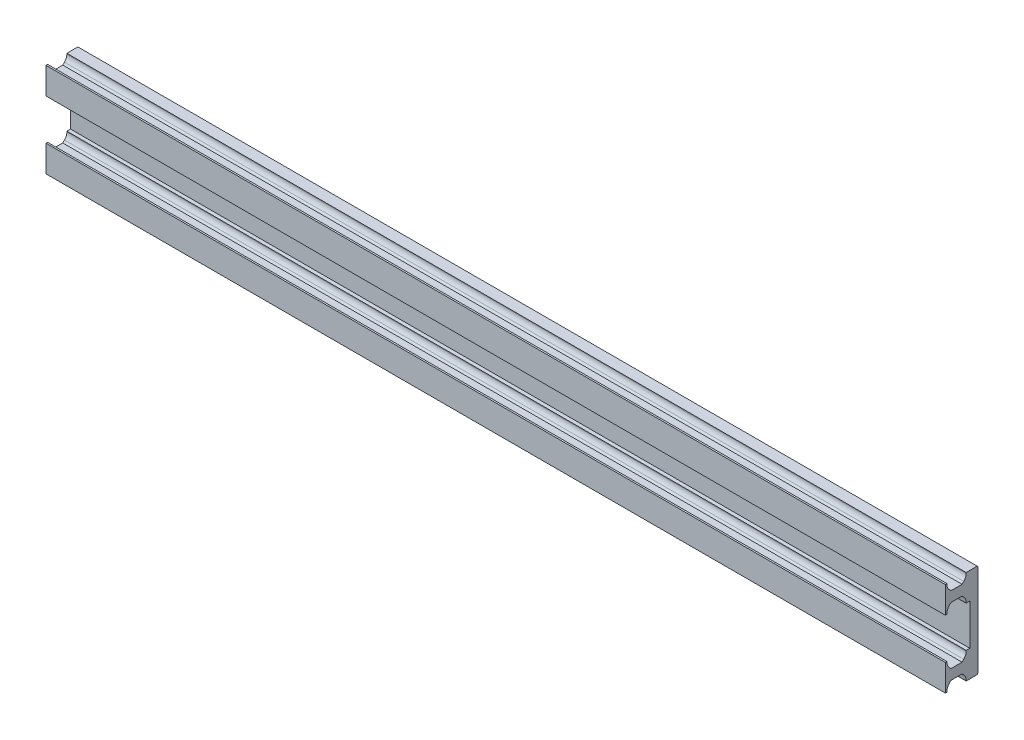
SolidWorks part; units mm, degrees
ref_plane "Front" through (0, 0, 0) normal (0, 0, 1) x (1, 0, 0)
ref_plane "Top" through (0, 0, 0) normal (0, 1, 0) x (1, 0, 0)
ref_plane "Right" through (0, 0, 0) normal (1, 0, 0) x (0, 0, -1)
sketch "Sketch1" plane through (0, 0, 0) normal (0, 0, 1) x (1, 0, 0)
  line L0 (-110, -4.5) -> (-110, 4.5) construction
  line L1 (110, 11.5) -> (-110, 11.5)
  line L2 (110, 11.5) -> (110, -11.5)
  line L3 (110, -11.5) -> (-110, -11.5)
  line L4 (-110, 11.5) -> (-110, -11.5)
  line L5 (110, 11.5) -> (-110, -11.5) construction
  line L6 (110, -11.5) -> (-110, 11.5) construction
  line L8 (110, 4.5) -> (-110, 4.5) construction
  point P0 (0, 0)
  dimension "D1" = 7
extrude "Boss-Extrude1" add sketch "Sketch1" against normal blind 2
sketch "Sketch2" plane through (0, 0, 0) normal (0, 0, 1) x (1, 0, 0)
  line L0 (-110, 11.5) -> (-110, -11.5) construction
  line L1 (110, 11.5) -> (-110, 11.5)
  line L2 (110, 11.5) -> (110, 5)
  line L3 (110, 5) -> (-110, 5)
  line L4 (-110, 11.5) -> (-110, 5)
  line L5 (110, -11.5) -> (110, 11.5) construction
  line L6 (110, -11.5) -> (-110, -11.5)
  line L7 (110, -11.5) -> (110, -5)
  line L8 (110, -5) -> (-110, -5)
  line L9 (-110, -11.5) -> (-110, -5)
  line L11 (110, 4.5) -> (-110, 4.5) construction
  dimension "D1" = 0.5
extrude "Boss-Extrude2" add sketch "Sketch2" along normal offset from surface (6 mm away) 1 up to face at (0, -11.5, -1)
ref_plane "Center of Slots" through (0, 8.25, 0) normal (0, -1, 0) x (-1, 0, 0)
sketch "Sketch5" plane through (0, 0, 0) normal (1, 0, 0) x (0, 0, -1)
  line L16 (-1.9, 7) -> (-4.6, 7)
  line L17 (-1.9, 7) -> (-4.6, 7)
  line L18 (-4.6, 7) -> (-5.0142, 6.5858)
  line L19 (-4.6, 7) -> (-5.0142, 6.5858)
  line L20 (-5.6, 5.1716) -> (-5.6, 4.3284)
  line L21 (-5.6, 5.1716) -> (-5.6, 4.3284)
  line L22 (-5.0142, 2.9142) -> (-4.6, 2.5)
  line L23 (-5.0142, 2.9142) -> (-4.6, 2.5)
  line L24 (-4.6, 2.5) -> (-1.9, 2.5)
  line L25 (-4.6, 2.5) -> (-1.9, 2.5)
  line L26 (-1.9, 2.5) -> (-1.4858, 2.9142)
  line L27 (-1.9, 2.5) -> (-1.4858, 2.9142)
  line L28 (-0.9, 4.3284) -> (-0.9, 5.1716)
  line L29 (-0.9, 4.3284) -> (-0.9, 5.1716)
  line L30 (-1.4858, 6.5858) -> (-1.9, 7)
  line L31 (-1.4858, 6.5858) -> (-1.9, 7)
  arc A12 (-5.0142, 6.5858) -> (-5.6, 5.1716) centre (-3.6, 5.1716) ccw
  arc A13 (-5.0142, 6.5858) -> (-5.6, 5.1716) centre (-3.6, 5.1716) ccw
  arc A14 (-5.6, 4.3284) -> (-5.0142, 2.9142) centre (-3.6, 4.3284) ccw
  arc A15 (-5.6, 4.3284) -> (-5.0142, 2.9142) centre (-3.6, 4.3284) ccw
  arc A16 (-1.4858, 2.9142) -> (-0.9, 4.3284) centre (-2.9, 4.3284) ccw
  arc A17 (-1.4858, 2.9142) -> (-0.9, 4.3284) centre (-2.9, 4.3284) ccw
  arc A18 (-0.9, 5.1716) -> (-1.4858, 6.5858) centre (-2.9, 5.1716) ccw
  arc A19 (-0.9, 5.1716) -> (-1.4858, 6.5858) centre (-2.9, 5.1716) ccw
  dimension "D1" = 0
extrude "Middle Slot" cut sketch "Sketch5" against normal through all both and the other way through all
mirror "Middle Slots" about plane through (0, 0, 0) normal (0, 1, 0) of "Middle Slot"
sketch "Sketch7" plane through (0, 0, 0) normal (1, 0, 0) x (0, 0, -1)
  line L8 (-1.875, 13.975) -> (-4.625, 13.975)
  line L9 (-4.625, 13.975) -> (-5.0142, 13.5858)
  line L10 (-5.6, 12.1716) -> (-5.6, 11.3284)
  line L11 (-5.0142, 9.9142) -> (-4.6, 9.5)
  line L12 (-4.6, 9.5) -> (-1.9, 9.5)
  line L13 (-1.9, 9.5) -> (-1.4858, 9.9142)
  line L14 (-0.9, 11.3284) -> (-0.9, 12.1716)
  line L15 (-1.4858, 13.5858) -> (-1.875, 13.975)
  line L16 (-1.875, 13.975) -> (-4.625, 13.975)
  line L17 (-4.625, 13.975) -> (-5.0142, 13.5858)
  line L18 (-5.6, 12.1716) -> (-5.6, 11.3284)
  line L19 (-5.0142, 9.9142) -> (-4.6, 9.5)
  line L20 (-4.6, 9.5) -> (-1.9, 9.5)
  line L21 (-1.9, 9.5) -> (-1.4858, 9.9142)
  line L22 (-0.9, 11.3284) -> (-0.9, 12.1716)
  line L23 (-1.4858, 13.5858) -> (-1.875, 13.975)
  arc A4 (-5.0142, 13.5858) -> (-5.6, 12.1716) centre (-3.6, 12.1716) ccw
  arc A5 (-5.6, 11.3284) -> (-5.0142, 9.9142) centre (-3.6, 11.3284) ccw
  arc A6 (-1.4858, 9.9142) -> (-0.9, 11.3284) centre (-2.9, 11.3284) ccw
  arc A7 (-0.9, 12.1716) -> (-1.4858, 13.5858) centre (-2.9, 12.1716) ccw
  arc A8 (-5.0142, 13.5858) -> (-5.6, 12.1716) centre (-3.6, 12.1716) ccw
  arc A9 (-5.6, 11.3284) -> (-5.0142, 9.9142) centre (-3.6, 11.3284) ccw
  arc A10 (-1.4858, 9.9142) -> (-0.9, 11.3284) centre (-2.9, 11.3284) ccw
  arc A11 (-0.9, 12.1716) -> (-1.4858, 13.5858) centre (-2.9, 12.1716) ccw
  dimension "D1" = 0
extrude "Top Slot" cut sketch "Sketch7" against normal through all both and the other way through all
mirror "Top Slots" about plane through (0, 0, 0) normal (0, 1, 0) of "Top Slot"
chamfer "Deburs" distance 0.2 angle 45 2 edges at (0, -11.5, -2) (0, 11.5, -2)
